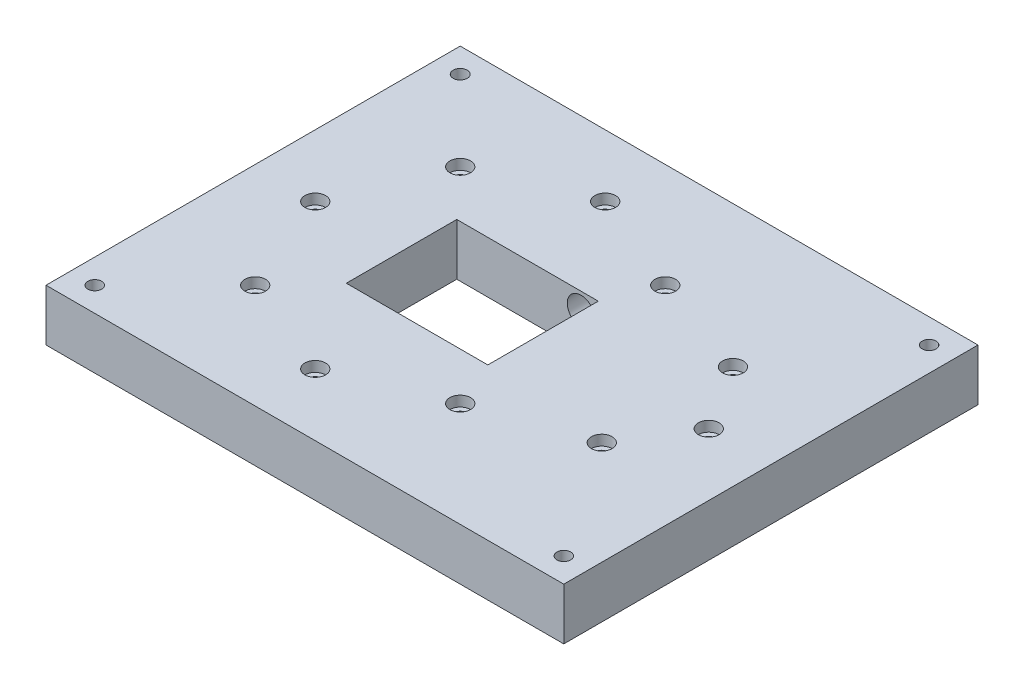
SolidWorks part; units mm, degrees
ref_plane "Front Plane" through (0, 0, 0) normal (0, 0, 1) x (1, 0, 0)
ref_plane "Top Plane" through (0, 0, 0) normal (0, 1, 0) x (1, 0, 0)
ref_plane "Right Plane" through (0, 0, 0) normal (1, 0, 0) x (0, 0, -1)
sketch "Sketch1" plane through (0, 0, 0) normal (0, 1, 0) x (1, 0, 0)
  line L8 (45, 0) -> (57, 0) construction
  line L16 (-15, 0) -> (-32, 0) construction
  line L17 (45, 19) -> (45, -19) construction
  line L18 (-75, -60) -> (-75, 60)
  line L19 (-75, 60) -> (75, 60)
  line L20 (75, 60) -> (75, -60)
  line L21 (75, -60) -> (-75, -60)
  line L22 (-15, 0) -> (14.6985, 29.6985) construction
  line L23 (-75, 60) -> (-67.9289, 52.9289) construction
  line L24 (75, -60) -> (67.9289, -52.9289) construction
  line L26 (-15, 0) -> (9, 0) construction
  line L27 (-15, -16) -> (-15, 16) construction
  line L28 (-32, -16) -> (-32, 16)
  line L29 (-32, 16) -> (9, 16)
  line L30 (9, 16) -> (9, -16)
  line L31 (9, -16) -> (-32, -16)
  circle A8 centre (-15, 0) radius 57 construction
  circle A27 centre (-15, 0) radius 42 construction
  circle A28 centre (14.6985, 29.6985) radius 1.55
  circle A29 centre (-15, 42) radius 1.55
  circle A30 centre (-44.6985, 29.6985) radius 1.55
  circle A31 centre (-57, 0) radius 1.55
  circle A32 centre (-44.6985, -29.6985) radius 1.55
  circle A33 centre (-15, -42) radius 1.55
  circle A34 centre (14.6985, -29.6985) radius 1.55
  circle A38 centre (45, 0) radius 27 construction
  circle A39 centre (45, -19) radius 1.55
  circle A40 centre (57, 0) radius 1.55
  circle A41 centre (45, 19) radius 1.55
  circle A42 centre (-67.9289, 52.9289) radius 2.05
  circle A43 centre (67.9289, -52.9289) radius 2
  circle A44 centre (-67.9289, -52.9289) radius 2
  circle A45 centre (67.9289, 52.9289) radius 2
  point P17 (45, 0)
  point P25 (-15, 0)
  point P28 (-15, 0)
  point P31 (-15, 0)
  point P36 (-15, 0)
  point P39 (-32, 0)
  point P53 (-15, 0)
  point P67 (-15, 0)
  dimension "D1" = 7
extrude "Boss-Extrude1" add sketch "Sketch1" along normal blind 15
sketch "Sketch2" plane through (0, 15, 0) normal (0, 1, 0) x (1, 0, 0)
  circle A0 centre (14.6985, 29.6985) radius 3
  circle A1 centre (-15, 42) radius 3
  circle A2 centre (-44.6985, 29.6985) radius 3
  circle A3 centre (-57, 0) radius 3
  circle A4 centre (-44.6985, -29.6985) radius 3
  circle A5 centre (-15, -42) radius 3
  circle A6 centre (14.6985, -29.6985) radius 3
  circle A10 centre (45, -19) radius 3
  circle A11 centre (57, 0) radius 3
  circle A12 centre (45, 19) radius 3
  point P5 (-15, 0)
  point P19 (-15, 0)
  dimension "D1" = 7
extrude "Cut-Extrude1" cut sketch "Sketch2" against normal blind 3
sketch "Sketch3" plane through (0, 0, -16) normal (0, 0, 1) x (1, 0, 0)
  line L0 (9, 0) -> (4, 0) construction
  line L3 (9, 0) -> (-32, 0) construction
  line L4 (4, 0) -> (4, 10) construction
  circle A2 centre (4, 10) radius 4
extrude "Cut-Extrude2" cut sketch "Sketch3" against normal blind 44
